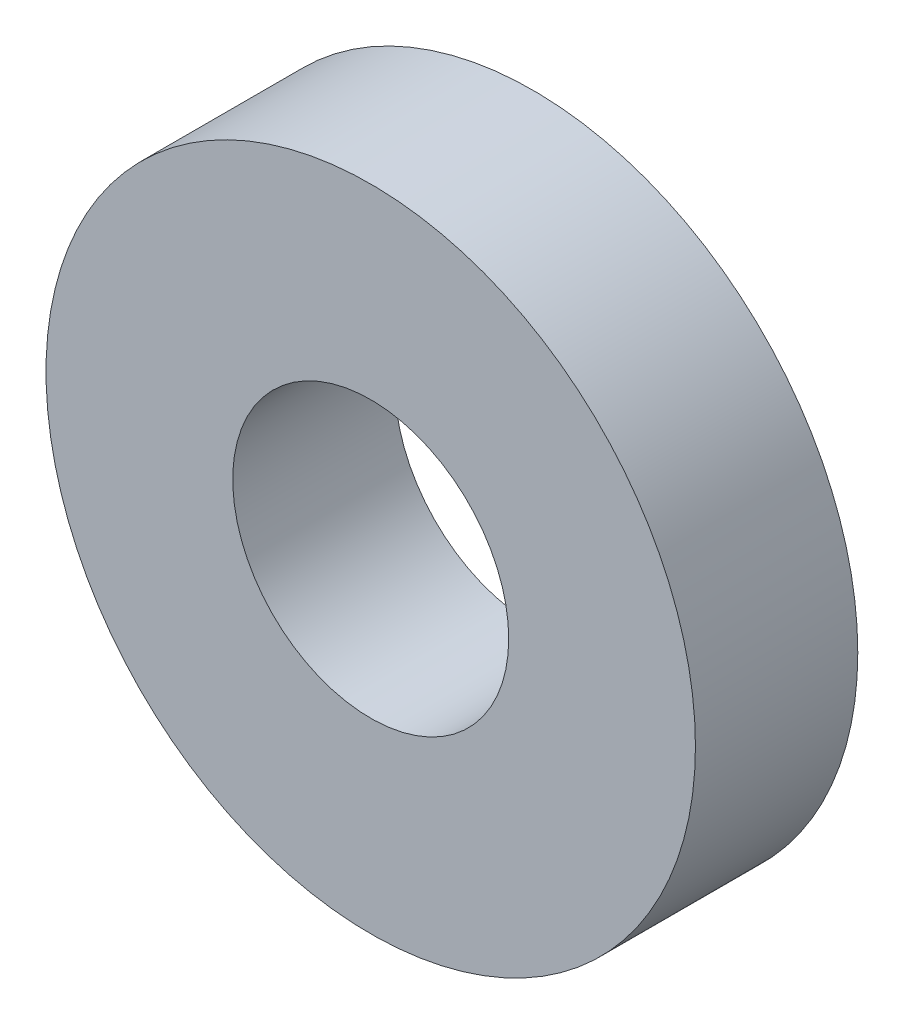
SolidWorks part; units mm, degrees
ref_plane "Front Plane" through (0, 0, 0) normal (0, 0, 1) x (1, 0, 0)
ref_plane "Top Plane" through (0, 0, 0) normal (0, 1, 0) x (1, 0, 0)
ref_plane "Right Plane" through (0, 0, 0) normal (1, 0, 0) x (0, 0, -1)
sketch "Çizim1" plane through (0, 0, 0) normal (0, 0, 1) x (1, 0, 0)
  circle A0 centre (0, 0) radius 10
  circle A1 centre (0, 0) radius 4.25
  dimension "D1" = 20
  dimension "D2" = 8.5
base flange "Taban-Flanş1" sketch "Çizim1" thickness 5 reverse thickness direction no parameters "D1"=0.7366
sketch "Büküm-Çizgileri1" [suppressed] plane through (0, 0, 0) normal (0, 1, 0) x (1, 0, 0)
sketch "Sınırlandırma-Kutusu1" [suppressed] plane through (0, 0, 0) normal (0, 1, 0) x (1, 0, 0)
sheet metal parameters "Sac-Levha1" thickness 5 parameters "D1"=0.7366
flat pattern "Düz-Çoğaltma1" [suppressed]
sketch "Büküm-Çizgileri2" plane through (0, 0, 0) normal (0, 1, 0) x (1, 0, 0)
sketch3d "Sınırlandırma-Kutusu2" [suppressed]
  line L0 (-9.9657, 10.0341, 0) -> (-10.0341, -9.9656, 0) construction
  line L1 (10.034, 9.9656, 0) -> (9.9656, -10.0341, 0) construction
  line L2 (-9.9657, 10.0341, 0) -> (10.034, 9.9656, 0) construction
  line L3 (-10.0341, -9.9656, 0) -> (9.9656, -10.0341, 0) construction
